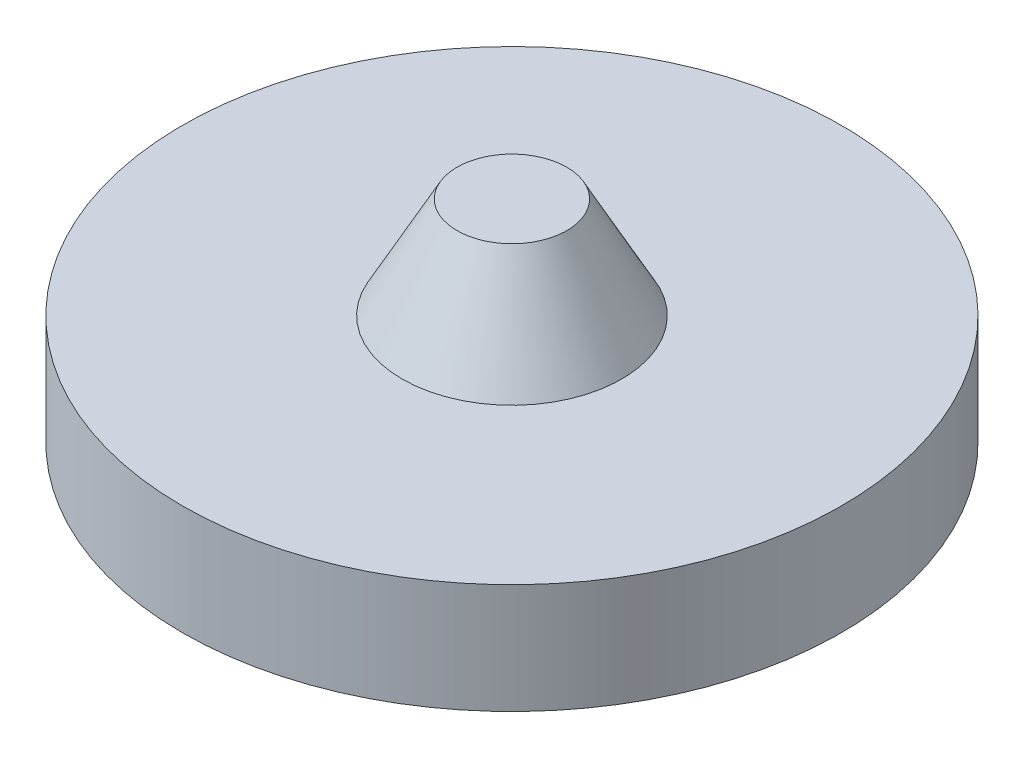
SolidWorks part; units mm, degrees
material "6061-T6 (SS)"
ref_plane "Front Plane" through (0, 0, 0) normal (0, 0, 1) x (1, 0, 0)
ref_plane "Top Plane" through (0, 0, 0) normal (0, 1, 0) x (1, 0, 0)
ref_plane "Right Plane" through (0, 0, 0) normal (1, 0, 0) x (0, 0, -1)
ref_axis "Axis1" through (0, 0, 55) along (0, 0, -1)
sketch "Sketch1" plane through (0, 0, 0) normal (0, 1, 0) x (1, 0, 0)
  circle A0 centre (0, 0) radius 6
  dimension "D1" = 12
extrude "Boss-Extrude1" add sketch "Sketch1" along normal mid plane 2
sketch "Sketch2" plane through (0, 1, 0) normal (0, 1, 0) x (1, 0, 0)
  circle A0 centre (0, 0) radius 2
  dimension "D1" = 4
sketch "Sketch3" plane through (0, 0, 0) normal (1, 0, 0) x (0, 0, -1)
  line L0 (0, 1) -> (0, 2.84) construction
  line L2 (6, 1) -> (-6, 1) construction
  line L3 (0, 1) -> (-2, 1)
  line L4 (-2, 1) -> (-1, 2.84)
  line L5 (-1, 2.84) -> (0, 2.84)
  line L6 (0, 1) -> (0, 2.84)
  point P5 (0, 1)
  dimension "D1" = 2
  dimension "D2" = 1
  dimension "D3" = 1.84
revolve "Revolve1" add sketch "Sketch3" angle 360 about L0
